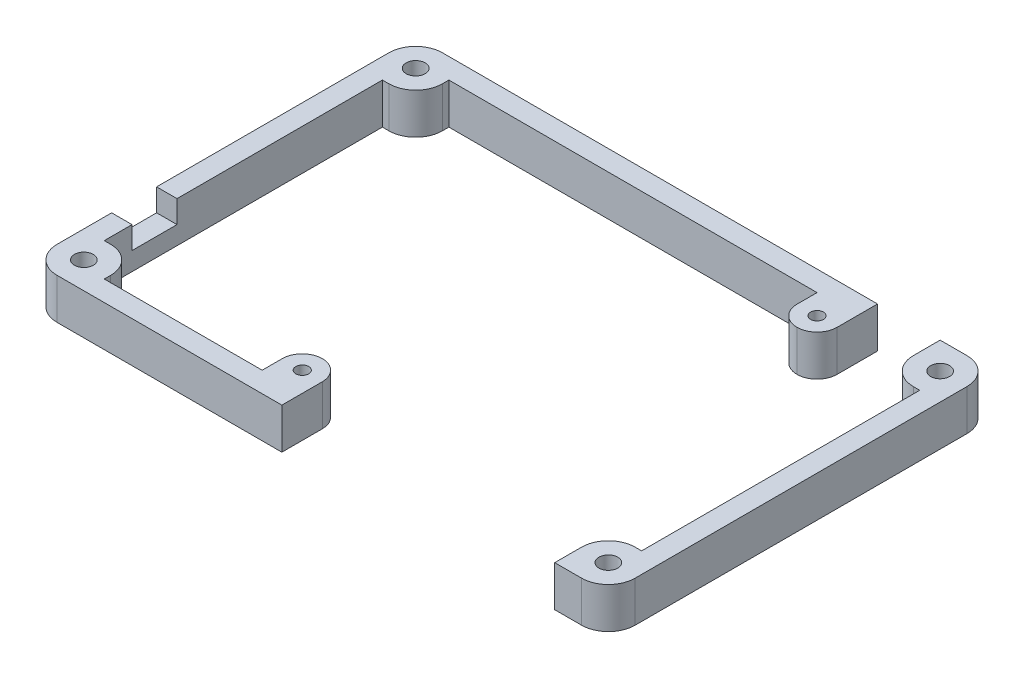
SolidWorks part; units mm, degrees
material "Rubber"
ref_plane "Front" through (0, 0, 0) normal (0, 0, 1) x (1, 0, 0)
ref_plane "Top" through (0, 0, 0) normal (0, 1, 0) x (1, 0, 0)
ref_plane "Right" through (0, 0, 0) normal (1, 0, 0) x (0, 0, -1)
sketch "Sketch1" plane through (0, 0, 0) normal (0, 1, 0) x (1, 0, 0)
  line L0 (-45, 0) -> (45, 0) construction
  line L1 (-45, 30) -> (45, 30) construction
  line L2 (-45, 30) -> (-45, -30) construction
  line L3 (-45, -30) -> (45, -30) construction
  line L4 (45, 30) -> (45, -30) construction
  line L5 (0, -30) -> (0, 30) construction
  line L6 (41.825, 26.825) -> (41.825, -26.825) construction
  line L7 (-41.825, -26.825) -> (41.825, -26.825) construction
  line L8 (-41.825, 26.825) -> (-41.825, -26.825) construction
  line L9 (-41.825, 26.825) -> (41.825, 26.825) construction
  line L10 (40.825, 25.825) -> (40.825, -25.825) construction
  line L11 (-40.825, -25.825) -> (40.825, -25.825) construction
  line L12 (-40.825, 25.825) -> (-40.825, -25.825) construction
  line L13 (-40.825, 25.825) -> (40.825, 25.825) construction
  line L14 (40.825, 21.65) -> (45, 21.65) construction
  line L15 (40.825, -21.65) -> (45, -21.65) construction
  line L16 (36.65, -25.825) -> (36.65, -30) construction
  line L17 (-36.65, -25.825) -> (-36.65, -30) construction
  line L18 (-40.825, -21.65) -> (-45, -21.65) construction
  line L19 (-36.65, 25.825) -> (-36.65, 30) construction
  line L20 (-40.825, 21.65) -> (-45, 21.65) construction
  line L21 (36.65, 25.825) -> (36.65, 30) construction
  line L22 (40.825, -25.825) -> (41.825, -25.825) construction
  circle A0 centre (-40.825, -25.825) radius 1 construction
  circle A1 centre (40.825, -25.825) radius 1 construction
  circle A2 centre (40.825, 25.825) radius 1 construction
  circle A3 centre (-40.825, 25.825) radius 1 construction
  circle A4 centre (40.825, -25.825) radius 4.175 construction
  circle A5 centre (40.825, 25.825) radius 4.175 construction
  circle A6 centre (-40.825, 25.825) radius 4.175 construction
  circle A7 centre (-40.825, -25.825) radius 4.175 construction
  dimension "D1" = 90
  dimension "D2" = 60
  dimension "D4" = 1
  dimension "D3" = 3.175
sketch "Sketch2" plane through (0, 0, 0) normal (0, 1, 0) x (1, 0, 0)
  line L0 (-45, 30) -> (-45, -30) construction
  line L1 (-45, -30) -> (45, -30) construction
  line L2 (45, 30) -> (45, -30) construction
  line L3 (-45, 30) -> (45, 30) construction
  line L4 (40.825, 21.65) -> (45, 21.65) construction
  line L5 (36.65, 25.825) -> (36.65, 30) construction
  line L6 (-36.65, 25.825) -> (-36.65, 30) construction
  line L7 (-40.825, 21.65) -> (-45, 21.65) construction
  line L8 (-36.65, -25.825) -> (-36.65, -30) construction
  line L9 (-40.825, -21.65) -> (-45, -21.65) construction
  line L10 (36.65, -25.825) -> (36.65, -30) construction
  line L11 (40.825, -21.65) -> (45, -21.65) construction
  line L16 (-45, 25.825) -> (-45, -25.825)
  line L17 (-40.825, -30) -> (40.825, -30)
  line L18 (45, 25.825) -> (45, -25.825)
  line L19 (-40.825, 30) -> (40.825, 30)
  line L20 (40.825, 21.65) -> (41.825, 21.65)
  line L21 (36.65, 25.825) -> (36.65, 26.825)
  line L22 (-36.65, 25.825) -> (-36.65, 26.825)
  line L23 (-40.825, 21.65) -> (-41.825, 21.65)
  line L24 (-36.65, -25.825) -> (-36.65, -26.825)
  line L25 (-40.825, -21.65) -> (-41.825, -21.65)
  line L26 (36.65, -25.825) -> (36.65, -26.825)
  line L27 (40.825, -21.65) -> (41.825, -21.65)
  line L28 (41.825, 26.825) -> (41.825, -26.825) construction
  line L29 (-36.65, -26.825) -> (36.65, -26.825)
  line L30 (-41.825, 26.825) -> (41.825, 26.825) construction
  line L31 (-41.825, 26.825) -> (-41.825, -26.825) construction
  line L32 (-36.65, 26.825) -> (36.65, 26.825)
  line L33 (-41.825, 21.65) -> (-41.825, -21.65)
  line L34 (41.825, 21.65) -> (41.825, -21.65)
  line L35 (-41.825, -26.825) -> (41.825, -26.825) construction
  circle A0 centre (40.825, 25.825) radius 4.175 construction
  circle A1 centre (40.825, 25.825) radius 1 construction
  circle A2 centre (-40.825, 25.825) radius 4.175 construction
  circle A3 centre (-40.825, 25.825) radius 1 construction
  circle A4 centre (-40.825, -25.825) radius 4.175 construction
  circle A5 centre (40.825, -25.825) radius 4.175 construction
  arc A6 (45, 25.825) -> (40.825, 30) centre (40.825, 25.825) ccw
  circle A7 centre (40.825, 25.825) radius 1 construction
  arc A8 (-40.825, 30) -> (-45, 25.825) centre (-40.825, 25.825) ccw
  circle A9 centre (-40.825, 25.825) radius 1 construction
  arc A10 (-36.65, -25.825) -> (-40.825, -21.65) centre (-40.825, -25.825) ccw
  arc A11 (40.825, -21.65) -> (36.65, -25.825) centre (40.825, -25.825) ccw
  circle A12 centre (-40.825, -25.825) radius 1 construction
  circle A13 centre (40.825, -25.825) radius 1 construction
  circle A14 centre (-40.825, -25.825) radius 1 construction
  circle A15 centre (40.825, -25.825) radius 1 construction
  arc A16 (-40.825, 21.65) -> (-36.65, 25.825) centre (-40.825, 25.825) ccw
  arc A17 (-45, -25.825) -> (-40.825, -30) centre (-40.825, -25.825) ccw
  arc A18 (40.825, -30) -> (45, -25.825) centre (40.825, -25.825) ccw
  arc A19 (36.65, 25.825) -> (40.825, 21.65) centre (40.825, 25.825) ccw
extrude "Boss-Extrude3" add sketch "Sketch2" along normal blind 6.35
sketch "Sketch3" plane through (0, 0, -30) normal (0, 0, -1) x (-1, 0, 0)
  line L0 (-40.825, 6.35) -> (40.825, 6.35) construction
  line L1 (-36.65, 6.35) -> (-26.9027, 6.35)
  line L2 (-36.65, 6.35) -> (-36.65, 0)
  line L3 (-36.65, 0) -> (-26.9027, 0)
  line L4 (-26.9027, 6.35) -> (-26.9027, 0)
  line L5 (-40.825, 0) -> (40.825, 0) construction
  line L6 (-40.5045, -11.2179) -> (-40.6503, -11.506) construction
extrude "Cut-Extrude1" cut sketch "Sketch3" against normal up to vertex (3.175 mm away) up to point (36.65, 6.35, -26.825)
sketch "Sketch4" plane through (0, 0, 30) normal (0, 0, 1) x (1, 0, 0)
  line L0 (-40.825, 6.35) -> (40.825, 6.35) construction
  line L1 (36.65, 6.35) -> (-5.825, 6.35)
  line L2 (36.65, 6.35) -> (36.65, 0)
  line L3 (36.65, 0) -> (-5.825, 0)
  line L4 (-5.825, 6.35) -> (-5.825, 0)
  line L5 (-40.825, 0) -> (40.825, 0) construction
  line L6 (-40.825, 6.35) -> (-40.825, 0) construction
  dimension "D1" = 35
extrude "Cut-Extrude2" cut sketch "Sketch4" against normal up to vertex (3.175 mm away) up to point (36.65, 6.35, 26.825)
sketch "Sketch5" plane through (-45, 0, 0) normal (-1, 0, 0) x (0, 0, 1)
  line L0 (13.825, 6.35) -> (25.825, 6.35) construction
  line L1 (25.825, 6.35) -> (25.825, 0) construction
  line L3 (10.325, 9.85) -> (17.325, 9.85)
  line L4 (10.325, 9.85) -> (10.325, 2.85)
  line L5 (10.325, 2.85) -> (17.325, 2.85)
  line L6 (17.325, 9.85) -> (17.325, 2.85)
  line L7 (10.325, 9.85) -> (17.325, 2.85) construction
  line L8 (10.325, 2.85) -> (17.325, 9.85) construction
  dimension "D1" = 12
  dimension "D2" = 7
  dimension "D3" = 7
extrude "Cut-Extrude3" cut sketch "Sketch5" against normal up to surface (3.175 mm away) up to face at (-41.825, 3.175, 0)
sketch "Sketch7" plane through (0, 0, 0) normal (0, -1, 0) x (1, 0, 0)
  circle A0 centre (-40.825, -25.825) radius 1.4732
  circle A1 centre (-40.825, 25.825) radius 1.4732
  circle A2 centre (40.825, 25.825) radius 1.4732
  circle A3 centre (40.825, -25.825) radius 1.4732
  dimension "D1" = 2.9464
  dimension "D2" = 2.9464
  dimension "D3" = 2.9464
  dimension "D4" = 2.9464
extrude "Cut-Extrude4" cut sketch "Sketch7" against normal blind 10
sketch "Sketch10" plane through (0, 0, 26.825) normal (0, 0, -1) x (-1, 0, 0)
  line L0 (36.65, 0) -> (5.825, 0) construction
  line L1 (5.825, 6.35) -> (12.065, 6.35)
  line L2 (5.825, 6.35) -> (5.825, 0)
  line L3 (5.825, 0) -> (12.065, 0)
  line L4 (12.065, 6.35) -> (12.065, 0)
  dimension "D1" = 6.24
extrude "Boss-Extrude4" add sketch "Sketch10" along normal blind 6.24
sketch "Sketch11" plane through (0, 0, -26.825) normal (0, 0, 1) x (1, 0, 0)
  line L0 (26.9027, 6.35) -> (-36.65, 6.35) construction
  line L1 (26.9027, 0) -> (20.6627, 0)
  line L2 (26.9027, 0) -> (26.9027, 6.35)
  line L3 (26.9027, 6.35) -> (20.6627, 6.35)
  line L4 (20.6627, 0) -> (20.6627, 6.35)
  dimension "D1" = 6.24
extrude "Boss-Extrude5" add sketch "Sketch11" along normal blind 6.24
sketch "Sketch12" plane through (0, 6.35, 0) normal (0, 1, 0) x (1, 0, 0)
  line L0 (20.6627, 26.825) -> (26.9027, 20.585) construction
  circle A0 centre (23.7827, 23.705) radius 1
sketch "Sketch13" plane through (0, 6.35, 0) normal (0, 1, 0) x (1, 0, 0)
  line L0 (-12.065, -26.825) -> (-5.825, -20.585) construction
  circle A0 centre (-8.945, -23.705) radius 1
extrude "Cut-Extrude5" cut sketch "Sketch12" against normal through all
extrude "Cut-Extrude6" cut sketch "Sketch13" against normal through all
fillet "Fillet1" radius 3.12 4 edges at (26.9027, 3.175, -20.585) (20.6627, 3.175, -20.585) (-5.825, 3.175, 20.585) (-12.065, 3.175, 20.585)
